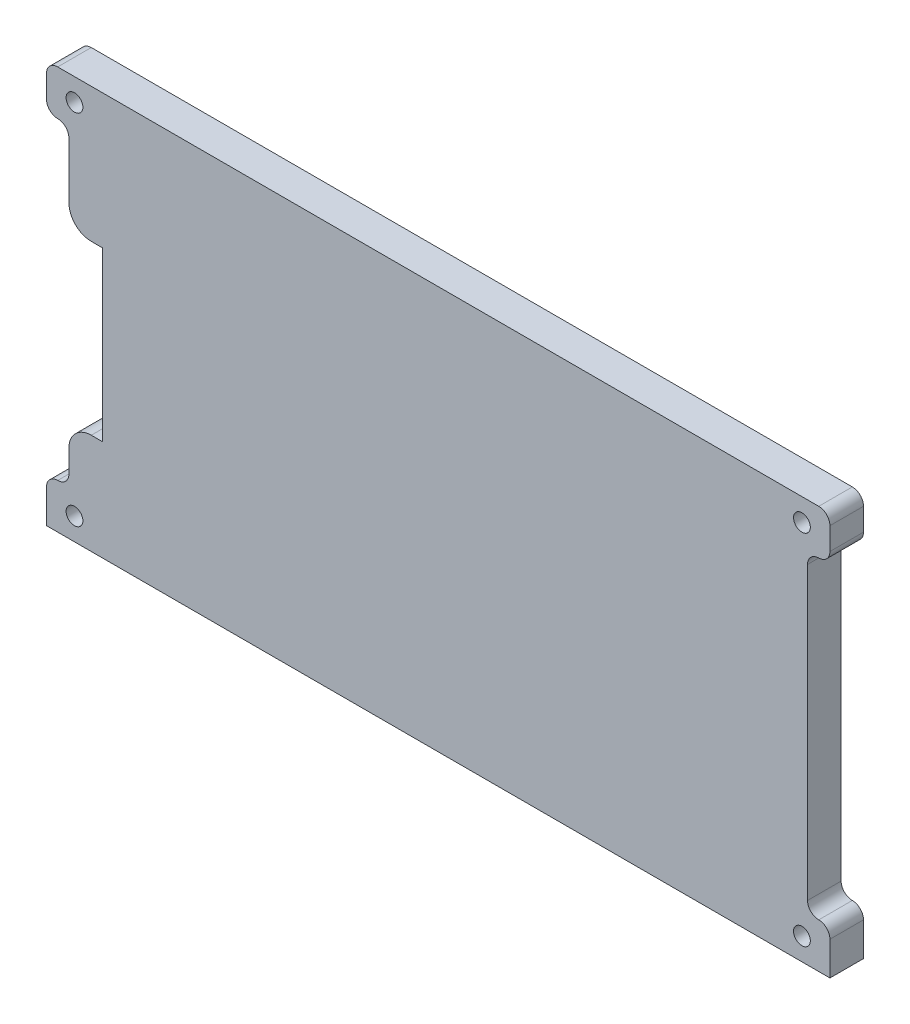
SolidWorks part; units mm, degrees
ref_plane "Front Plane" through (0, 0, 0) normal (0, 0, 1) x (1, 0, 0)
ref_plane "Top Plane" through (0, 0, 0) normal (0, 1, 0) x (1, 0, 0)
ref_plane "Right Plane" through (0, 0, 0) normal (1, 0, 0) x (0, 0, -1)
sketch "Sketch1" plane through (0, 0, 0) normal (0, 0, 1) x (1, 0, 0)
  line L1 (-33, -18) -> (33, -18)
  line L2 (-33, -18) -> (-33, 18)
  line L3 (-33, 18) -> (33, 18)
  line L4 (33, -18) -> (33, 18)
  line L5 (-33, -18) -> (33, 18) construction
  line L6 (-33, 18) -> (33, -18) construction
  point P0 (0, 0)
  dimension "D1" = 66
  dimension "D2" = 36
extrude "Boss-Extrude1" add sketch "Sketch1" along normal blind 3
sketch "Sketch2" plane through (0, 0, 3) normal (0, 0, 1) x (1, 0, 0)
  line L0 (0, 0) -> (-33, 0) construction
  line L1 (-33, 18) -> (-35, 18)
  line L2 (-33, 18) -> (-33, 14)
  line L3 (-33, 14) -> (-35, 14)
  line L4 (-35, 18) -> (-35, 14)
  line L5 (-33, 18) -> (-33, -18) construction
  line L6 (0, 0) -> (0, 18) construction
  line L7 (33, 18) -> (-33, 18) construction
  line L8 (-33, -14) -> (-35, -14)
  line L9 (-35, -18) -> (-35, -14)
  line L10 (-33, -18) -> (-35, -18)
  line L11 (-33, -18) -> (-33, -14)
  line L12 (33, 14) -> (35, 14)
  line L13 (35, 18) -> (35, 14)
  line L14 (33, 18) -> (35, 18)
  line L15 (33, 18) -> (33, 14)
  line L16 (33, -18) -> (33, -14)
  line L17 (33, -18) -> (35, -18)
  line L18 (35, -18) -> (35, -14)
  line L19 (33, -14) -> (35, -14)
  dimension "D1" = 2
  dimension "D2" = 4
extrude "Boss-Extrude3" add sketch "Sketch2" against normal blind 3
sketch "Sketch3" plane through (0, 0, 3) normal (0, 0, 1) x (1, 0, 0)
  line L0 (35, 18) -> (-35, 18) construction
  line L1 (-35, 18) -> (-35, 14) construction
  line L2 (0, 0) -> (0, 18) construction
  line L3 (0, 0) -> (-33, 0) construction
  line L4 (-33, 14) -> (-33, -14) construction
  circle A0 centre (-32.5, 16) radius 0.75
  circle A1 centre (-32.5, -16) radius 0.75
  circle A2 centre (32.5, -16) radius 0.75
  circle A3 centre (32.5, 16) radius 0.75
  dimension "D1" = 1.5
  dimension "D2" = 2
  dimension "D3" = 2.5
extrude "Cut-Extrude1" cut sketch "Sketch3" against normal through all
sketch "Sketch4" plane through (0, 0, 3) normal (0, 0, 1) x (1, 0, 0)
  line L0 (0, 0) -> (-33, 0) construction
  line L1 (-33, 14) -> (-33, -14) construction
  line L3 (-33, 6) -> (-30, 6)
  line L4 (-33, 6) -> (-33, -9)
  line L5 (-33, -9) -> (-30, -9)
  line L6 (-30, 6) -> (-30, -9)
  dimension "D1" = 3
  dimension "D2" = 6
  dimension "D3" = 15
extrude "Cut-Extrude2" cut sketch "Sketch4" against normal through all
fillet "Fillet2" radius 2 2 edges at (-33, 6, 1.5) (-33, -9, 1.5)
fillet "Fillet3" radius 1 10 edges at (35, -14, 1.5) (33, -14, 1.5) (33, 14, 1.5) (35, 14, 1.5) (35, 18, 1.5) (-35, 18, 1.5) (-35, 14, 1.5) (-33, 14, 1.5) (-33, -14, 1.5) (-35, -14, 1.5)
